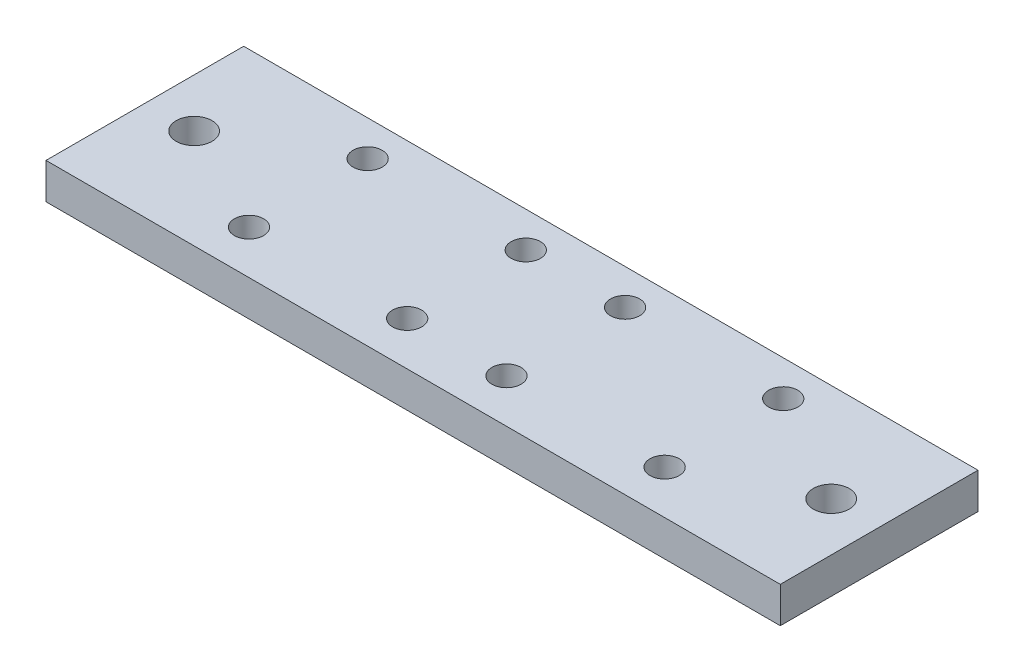
SolidWorks part; units mm, degrees
material "Alumina"
ref_plane "Front Plane" through (0, 0, 0) normal (0, 0, 1) x (1, 0, 0)
ref_plane "Top Plane" through (0, 0, 0) normal (0, 1, 0) x (1, 0, 0)
ref_plane "Right Plane" through (0, 0, 0) normal (1, 0, 0) x (0, 0, -1)
sketch "Sketch1" plane through (0, 0, 0) normal (0, 1, 0) x (1, 0, 0)
  line L1 (0, 0) -> (130, 0)
  line L2 (0, 0) -> (0, -35)
  line L3 (0, -35) -> (130, -35)
  line L4 (130, 0) -> (130, -35)
  dimension "D1" = 130
  dimension "D2" = 35
extrude "Boss-Extrude1" add sketch "Sketch1" along normal blind 6.35
sketch "Sketch5" plane through (0, 6.35, 0) normal (0, 1, 0) x (1, 0, 0)
  line L1 (0, 0) -> (0, -35) construction
  line L2 (130, -35) -> (130, 0) construction
  circle A0 centre (8.605, -17.3826) radius 3.18
  circle A2 centre (121.395, -17.3826) radius 3.18
  dimension "D1" = 8.605
  dimension "D2" = 8.605
extrude "Cut-Extrude2" cut sketch "Sketch5" against normal through all
sketch "Sketch8" plane through (0, 0, 0) normal (0, -1, 0) x (1, 0, 0)
  circle A16 centre (28.2094, 6.2712) radius 2.5866 construction
  circle A17 centre (28.2094, 27.2712) radius 2.5866 construction
  circle A18 centre (56.2094, 27.2712) radius 2.5866 construction
  circle A19 centre (56.2094, 6.2712) radius 2.5866 construction
  circle A20 centre (73.7914, 6.2712) radius 2.5866 construction
  circle A21 centre (73.7914, 27.2712) radius 2.5866 construction
  circle A22 centre (101.7914, 6.2712) radius 2.5866 construction
  circle A23 centre (101.7914, 27.2712) radius 2.5866 construction
  circle A24 centre (28.2094, 6.2712) radius 2.5866
  circle A25 centre (28.2094, 27.2712) radius 2.5866
  circle A26 centre (56.2094, 27.2712) radius 2.5866
  circle A27 centre (56.2094, 6.2712) radius 2.5866
  circle A28 centre (73.7914, 6.2712) radius 2.5866
  circle A29 centre (73.7914, 27.2712) radius 2.5866
  circle A30 centre (101.7914, 6.2712) radius 2.5866
  circle A31 centre (101.7914, 27.2712) radius 2.5866
extrude "Cut-Extrude4" cut sketch "Sketch8" against normal through all
